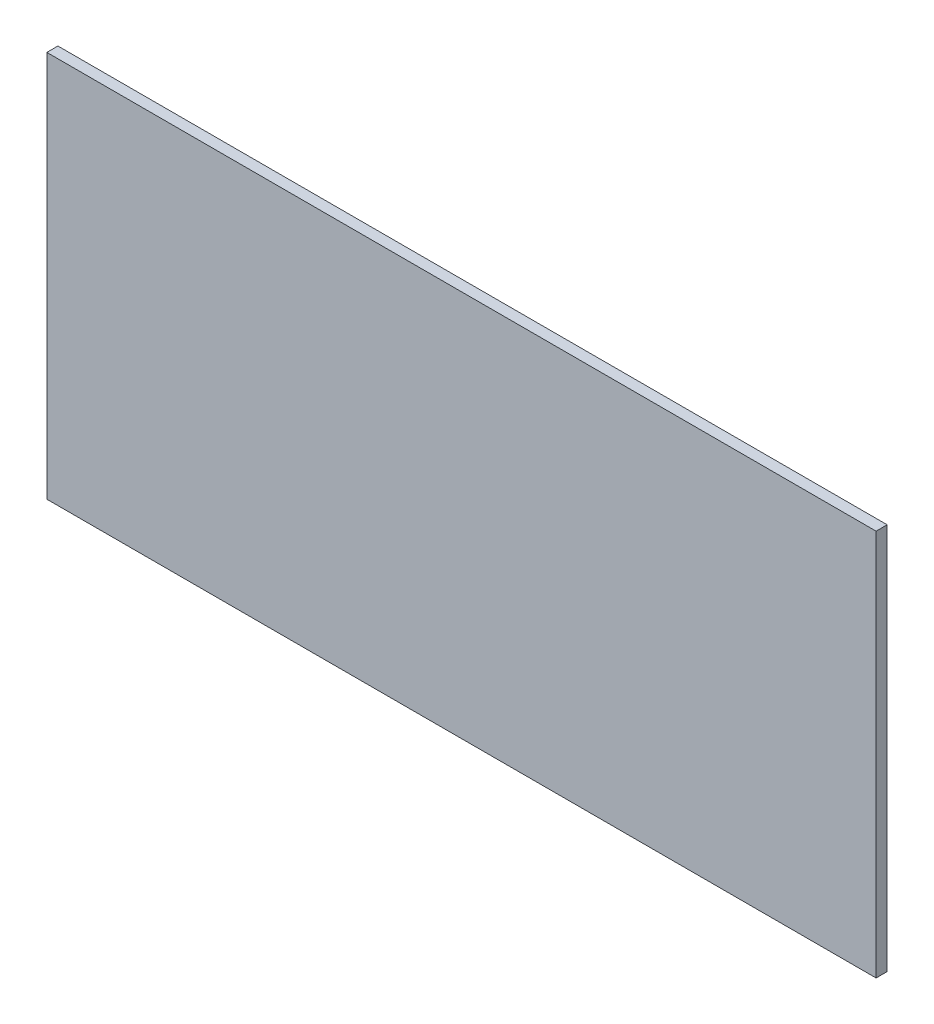
SolidWorks part; units mm, degrees
material "Brass"
ref_plane "Front Plane" through (0, 0, 0) normal (0, 0, 1) x (1, 0, 0)
ref_plane "Top Plane" through (0, 0, 0) normal (0, 1, 0) x (1, 0, 0)
ref_plane "Right Plane" through (0, 0, 0) normal (1, 0, 0) x (0, 0, -1)
sketch "Sketch1" plane through (0, 0, 0) normal (0, 0, 1) x (1, 0, 0)
  line L0 (0, 0) -> (300, 0)
  line L1 (300, 0) -> (300, 140)
  line L2 (300, 140) -> (0, 140)
  line L3 (0, 140) -> (0, 0)
  dimension "D1" = 300
  dimension "D2" = 140
extrude "Boss-Extrude1" add sketch "Sketch1" along normal blind 4
sketch "Sketch2" plane through (0, 0, 0) normal (0, 0, 1) x (1, 0, 0)
  circle A0 centre (15, 15) radius 1.5
  circle A1 centre (15, 124) radius 1.5
  circle A2 centre (287, 15) radius 1.5
  circle A3 centre (287, 124) radius 1.5
  dimension "D3" = 3
  dimension "D6" = 3
  dimension "D9" = 3
  dimension "D12" = 3
  dimension "D1" = 15
  dimension "D2" = 15
  dimension "D4" = 15
  dimension "D5" = 124
  dimension "D7" = 287
  dimension "D8" = 15
  dimension "D10" = 287
  dimension "D11" = 124
extrude "Cut-Extrude1" cut sketch "Sketch2" against normal mid plane 7
ref_axis "Axis1" through (-15, 0, 0) along (1, 0, 0)
